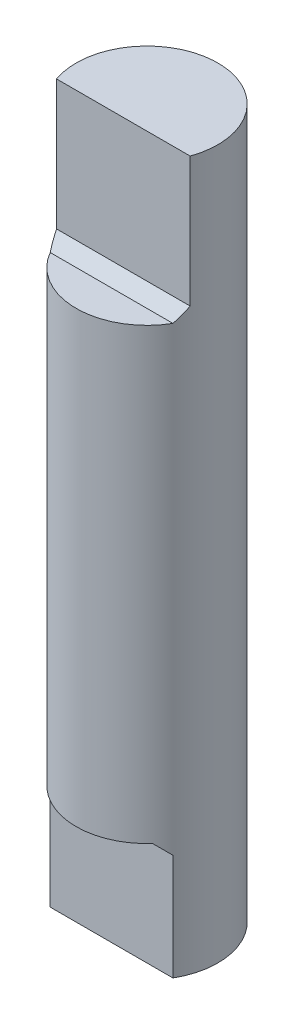
SolidWorks part; units mm, degrees
ref_plane "Alzado" through (0, 0, 0) normal (0, 0, 1) x (1, 0, 0)
ref_plane "Planta" through (0, 0, 0) normal (0, 1, 0) x (1, 0, 0)
ref_plane "Vista lateral" through (0, 0, 0) normal (1, 0, 0) x (0, 0, -1)
sketch "Croquis1" plane through (0, 0, 0) normal (0, 1, 0) x (1, 0, 0)
  circle A0 centre (0, 0) radius 3
  dimension "D1" = 6
extrude "Saliente-Extruir1" add sketch "Croquis1" along normal mid plane 30
sketch "Croquis3" plane through (0, 15, 0) normal (0, 1, 0) x (1, 0, 0)
  line L1 (-3.8744, -1) -> (4.3498, -1)
  line L2 (-3.8744, -1) -> (-3.8744, -3)
  line L3 (-3.8744, -3) -> (4.3498, -3)
  line L4 (4.3498, -1) -> (4.3498, -3)
  circle A0 centre (0, 0) radius 3 construction
  dimension "D1" = 2
  dimension "D2" = 1
extrude "Cortar-Extruir2" cut sketch "Croquis3" against normal blind 6 and the other way through all
sketch "Croquis4" plane through (0, 15, 0) normal (0, 1, 0) x (1, 0, 0)
  point P0 (0, 0)
chamfer "Chaflán1" distance 0.5 angle 45 1 edges at (0, 9, 1)
ref_axis "Eje1" through (0, 15, 0) along (0, -1, 0)
sketch "Croquis7" plane through (0, -15, 0) normal (0, -1, 0) x (1, 0, 0)
  line L0 (-2.5981, 1.5) -> (2.5981, 1.5)
  circle A0 centre (0, 0) radius 3 construction
  arc A1 (2.5981, 1.5) -> (-2.5981, 1.5) centre (0, 0) ccw
  dimension "D1" = 1.5
extrude "Cortar-Extruir3" cut sketch "Croquis7" against normal blind 5
chamfer "Chaflán2" distance 0.5 angle 45 1 edges at (0, -10, 1.5)
